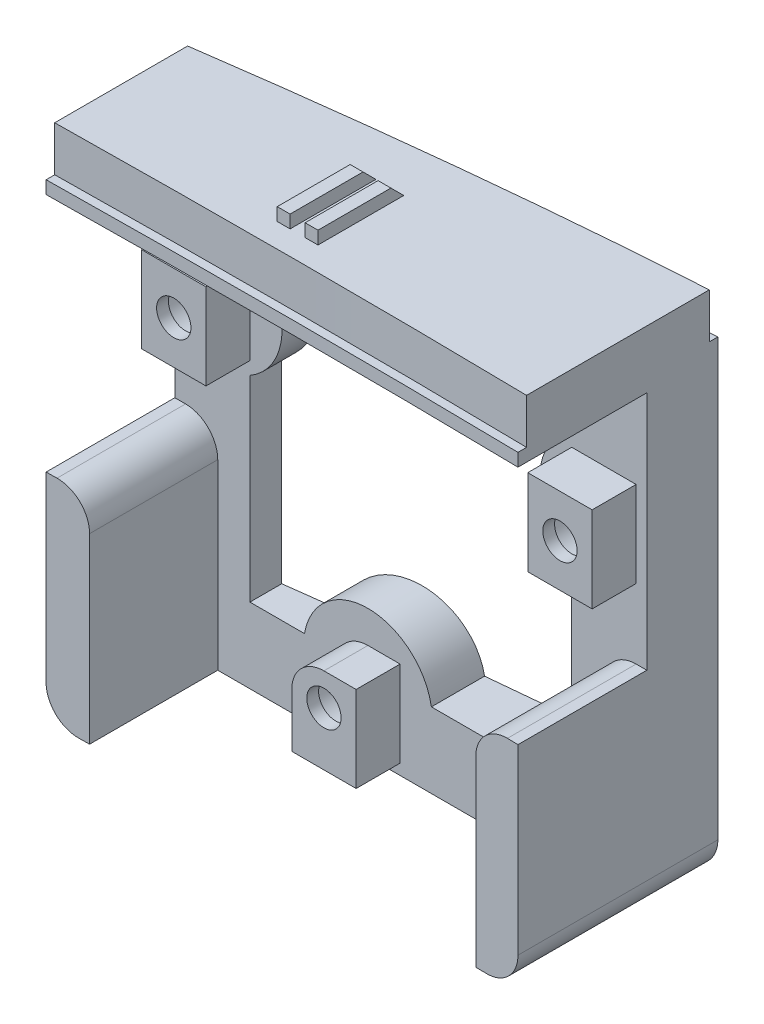
SolidWorks part; units mm, degrees
ref_plane "Front Plane" through (0, 0, 0) normal (0, 0, 1) x (1, 0, 0)
ref_plane "Top Plane" through (0, 0, 0) normal (0, 1, 0) x (1, 0, 0)
ref_plane "Right Plane" through (0, 0, 0) normal (1, 0, 0) x (0, 0, -1)
sketch "Sketch1" plane through (0, 0, 0) normal (0, 1, 0) x (1, 0, 0)
  line L0 (-144.1303, -12.9929) -> (155.8697, -12.8308) construction
  line L1 (-29.3738, 9.8314) -> (-29.3738, -4.1686)
  line L2 (14.6262, 14.4548) -> (14.6262, -4.183)
  line L5 (-29.3738, -2.9686) -> (14.6262, -2.9686)
  line L12 (-51.1303, 9.4041) -> (-59.1513, -7.7971) construction
  line L13 (-109.8536, -6.9996) -> (-109.986, -6.1605)
  line L14 (-11.0303, 7.0314) -> (-9.8303, 7.0314)
  line L15 (-11.0303, 7.0314) -> (-11.0303, -0.9686)
  line L16 (-11.0303, -0.9686) -> (-9.8303, -0.9686)
  line L17 (-9.8303, 7.0314) -> (-9.8303, -0.9686)
  line L18 (-8.4303, 7.0314) -> (-7.2303, 7.0314)
  line L19 (-8.4303, 7.0314) -> (-8.4303, -0.9686)
  line L20 (-8.4303, -0.9686) -> (-7.2303, -0.9686)
  line L21 (-7.2303, 7.0314) -> (-7.2303, -0.9686)
  circle A2 centre (-36.6303, 2.3202) radius 4.25
  arc A9 (-58.7697, -6.9788) -> (-58.7632, -6.9861) centre (-51.1303, -0.0856) ccw
  ellipse E0 centre (-36.6303, 2.3202) end of major axis (-36.1292, -4.0323) minor radius 5.05
  spline S0 degree 13 poles (-110.7235, -3.2524) (-98.8326, -0.2567) (-86.3944, 2.6358) (-73.4943, 5.427) (-60.2589, 8.0815) (-46.8275, 10.5453) (-33.3355, 12.7584) (-19.9065, 14.665) (-6.6486, 16.2187) (6.3449, 17.3865) (18.9944, 18.15) (31.2324, 18.5052) (43.0009, 18.4619) (54.25, 18.0415) knots 0.038912 0.038912 0.038912 0.038912 0.038912 0.038912 0.038912 0.038912 0.038912 0.038912 0.038912 0.038912 0.038912 0.038912 0.206425 0.206425 0.206425 0.206425 0.206425 0.206425 0.206425 0.206425 0.206425 0.206425 0.206425 0.206425 0.206425 0.206425
  spline S1 degree 3 poles (-105.7874, -5.9402) (-105.4515, -5.8576) (-103.7907, -5.4506) (-99.0842, -4.3142) (-91.5415, -2.5615) (-82.0457, -0.4684) (-69.1527, 2.2208) (-52.7063, 5.3568) (-32.7854, 8.6244) (-12.9944, 11.2716) (3.1558, 12.8711) (15.7533, 13.7541) (25.0163, 14.2135) (32.556, 14.4255) (38.4824, 14.4928) (41.3869, 14.4927) (42.8464, 14.4842) knots 0.043242 0.043242 0.043242 0.043242 0.044325 0.048583 0.058255 0.067926 0.077598 0.096941 0.116284 0.135628 0.154971 0.164642 0.174314 0.183986 0.188821 0.193657 0.193657 0.193657 0.193657
  spline S2 degree 3 poles (42.3412, -4.3021) (39.1703, -4.1474) (32.8439, -3.8739) (20.0493, -3.4589) (3.9637, -3.1861) (-15.3945, -3.1849) (-34.7131, -3.4228) (-53.9413, -3.8315) (-69.8279, -4.2978) (-82.3956, -4.7634) (-91.7251, -5.1693) (-99.1578, -5.5509) (-103.8174, -5.8207) (-105.4427, -5.9191) (-105.7874, -5.9402) knots 0.702444 0.702444 0.702444 0.702444 0.71714 0.731836 0.761227 0.790619 0.820011 0.849403 0.878795 0.89349 0.908186 0.922882 0.929138 0.930826 0.930826 0.930826 0.930826
  spline S3 degree 3 poles (-109.986, -6.1605) (-109.4642, -6.0291) (-108.4175, -5.7667) (-103.5943, -4.5692) (-94.8971, -2.4925) (-82.0108, 0.3758) (-63.7471, 4.1371) (-40.3543, 8.3552) (-16.9896, 11.6162) (1.2883, 13.4985) (14.7075, 14.5233) (27.7627, 15.1448) (36.8021, 15.2972) (42.0404, 15.2892) (43.1567, 15.2825) (43.6671, 15.2784) knots 0.038912 0.038912 0.038912 0.038912 0.040616 0.04232 0.054528 0.06816 0.081792 0.109056 0.13632 0.149952 0.163584 0.177216 0.190848 0.192861 0.194565 0.194565 0.194565 0.194565
  spline S4 degree 13 poles (52.5193, -8.6666) (40.2713, -7.9192) (27.7839, -7.3485) (15.1503, -6.9773) (2.4425, -6.804) (-10.2886, -6.8041) (-23.0116, -6.9375) (-35.7087, -7.1592) (-48.3688, -7.4339) (-60.9767, -7.7494) (-73.5011, -8.1244) (-85.8777, -8.6024) (-97.9897, -9.2254) (-109.6522, -9.993) knots 0.686195 0.686195 0.686195 0.686195 0.686195 0.686195 0.686195 0.686195 0.686195 0.686195 0.686195 0.686195 0.686195 0.686195 0.937578 0.937578 0.937578 0.937578 0.937578 0.937578 0.937578 0.937578 0.937578 0.937578 0.937578 0.937578 0.937578 0.937578
  spline S5 degree 3 poles (-110.5235, -4.0272) (-108.9029, -3.6189) (-105.6763, -2.8183) (-99.0735, -1.2268) (-90.6514, 0.7176) (-80.2925, 2.9758) (-67.9991, 5.4979) (-58.7506, 7.2436) (-50.652, 8.6798) (-47.6807, 9.1904) (-44.5606, 9.7093) (-38.2765, 10.745) (-25.0157, 12.7601) (-5.2278, 15.1631) (12.1229, 16.5847) (25.5727, 17.2429) (35.4177, 17.4948) (43.3901, 17.504) (49.633, 17.3925) (52.6803, 17.2987) (54.2127, 17.2415) knots 0.038912 0.038912 0.038912 0.038912 0.044146 0.049381 0.059851 0.07032 0.08079 0.096446 0.097403 0.1044 0.105092 0.106475 0.122668 0.143607 0.164546 0.175016 0.185486 0.195955 0.20119 0.206425 0.206425 0.206425 0.206425
  spline S6 degree 3 poles (52.5681, -7.868) (50.9024, -7.7664) (47.578, -7.5733) (40.8667, -7.2231) (32.4163, -6.8574) (22.195, -6.5335) (8.4979, -6.2488) (-8.6998, -6.1472) (-26.1679, -6.3047) (-37.8303, -6.5029) (-44.675, -6.6412) (-49.0049, -6.7375) (-53.5282, -6.8475) (-56.9797, -6.937) (-62.6027, -7.0912) (-70.3002, -7.3251) (-80.3346, -7.6831) (-90.3076, -8.1048) (-98.4897, -8.5174) (-104.9445, -8.8903) (-108.1134, -9.09) (-109.7048, -9.1947) knots 0.686195 0.686195 0.686195 0.686195 0.69405 0.701906 0.717617 0.733329 0.74904 0.780463 0.811886 0.82883 0.833892 0.843309 0.848739 0.854731 0.859237 0.874732 0.890444 0.906155 0.921867 0.929722 0.937578 0.937578 0.937578 0.937578
  spline S7 degree 3 poles (43.1189, -5.1414) (42.5664, -5.1139) (40.3515, -5.0059) (33.6908, -4.7068) (23.0612, -4.3421) (5.0464, -3.9837) (-17.5716, -3.9643) (-44.6283, -4.3923) (-66.9803, -4.9899) (-84.5965, -5.6437) (-96.3916, -6.1935) (-104.7586, -6.6717) (-108.8142, -6.9312) (-109.8536, -6.9996) knots 0.701175 0.701175 0.701175 0.701175 0.703751 0.711493 0.7321 0.752708 0.793923 0.835139 0.876354 0.896962 0.917569 0.932426 0.937578 0.937578 0.937578 0.937578
  spline S8 degree 3 poles (43.0791, -5.9404) (39.8994, -5.7822) (33.5559, -5.5021) (20.7207, -5.0752) (4.577, -4.7906) (-14.8622, -4.781) (-29.9542, -4.963) (-38.7515, -5.1226) (-41.4966, -5.1769) (-43.935, -5.226) (-46.8305, -5.2883) (-49.9812, -5.3611) (-51.9548, -5.4083) (-59.5635, -5.5969) (-69.6735, -5.894) (-82.18, -6.356) (-91.5501, -6.7627) (-99.2415, -7.157) (-105.3139, -7.5106) (-108.2984, -7.6991) (-109.7967, -7.7977) knots 0.701175 0.701175 0.701175 0.701175 0.71595 0.730726 0.760276 0.789826 0.819377 0.829214 0.830132 0.831967 0.840401 0.843428 0.846456 0.849484 0.878477 0.893252 0.908028 0.922803 0.93019 0.937578 0.937578 0.937578 0.937578
  spline S9 degree 3 poles (-110.1814, -5.3848) (-108.6794, -5.0063) (-105.6878, -4.2632) (-99.5742, -2.785) (-91.7846, -0.9758) (-82.2124, 1.1324) (-69.613, 3.7573) (-59.5108, 5.6872) (-50.135, 7.3499) (-46.7114, 7.9355) (-40.1955, 9.0106) (-29.5503, 10.6773) (-12.6029, 12.9298) (3.6765, 14.5228) (16.3735, 15.3941) (25.7087, 15.8415) (33.3064, 16.0409) (39.2778, 16.0967) (42.204, 16.0903) (43.6745, 16.0785) knots 0.038912 0.038912 0.038912 0.038912 0.043776 0.04864 0.058368 0.068097 0.077825 0.096092 0.09776 0.105207 0.106069 0.116738 0.136195 0.155652 0.16538 0.175108 0.184837 0.189701 0.194565 0.194565 0.194565 0.194565
  dimension "D1" = 8.5
  dimension "D2" = 14
  dimension "D3" = 44
  dimension "D4" = 1.2
  dimension "D5" = 26.8
  dimension "D6" = 28.2
  dimension "D7" = 8
  dimension "D8" = 8
  dimension "D9" = 2
  dimension "D10" = 2
  dimension "D11" = 1.2
  dimension "D12" = 1.2
extrude "Boss-Extrude2" add sketch "Sketch1" against normal blind 47.8 contours S3 L1 S1 L2 | S1 L1 L5 L2 | S2 L2 L5 L1 | S7 L2 S2 L1 | L17 L14 L15 L16 | L21 L18 L19 L20 region at (-7.4038, 0, -12.035) region at (-6.1165, 0, -4.438) region at (-7.397, 0, 3.1176) region at (-7.3732, 0, 3.6567) region at (-10.4303, 0, -3.0314) region at (-7.8303, 0, -3.0314)
extrude "Cut-Extrude1" cut sketch "Sketch1<3>" against normal blind 4.2 contours S7 L2 S2 L1 | S3 L1 S1 L2 region at (-7.4038, 0, -12.035) region at (-7.3732, 0, 3.6567)
sketch "Sketch1<3>" plane through (0, 0, 0) normal (0, 1, 0) x (1, 0, 0) same geometry as "Sketch1"
sketch "Sketch2" plane through (0, 0, 0) normal (0, 1, 0) x (1, 0, 0)
  line L0 (-29.3738, 7.8314) -> (14.6262, 7.8314)
  line L1 (-29.3738, 9.8314) -> (-29.3738, -4.1686) construction
  line L2 (14.6262, 14.4548) -> (14.6262, -4.183) construction
  line L3 (-29.3738, -2.9686) -> (14.6262, -2.9686) construction
  line L4 (-29.3738, -2.9686) -> (14.6262, -2.9686)
  line L5 (14.6262, 14.4548) -> (14.6262, -4.183)
  line L6 (-29.3738, 9.8314) -> (-29.3738, -4.1686)
  spline S0 degree 3 poles (-1947.4588, -167.681) (424.4026, -117.2665) (271.9813, -15.4064) (33.6908, -4.7068) (23.0612, -4.3421) (5.0464, -3.9837) (-17.5716, -3.9643) (-44.6283, -4.3923) (-66.9803, -4.9899) (-84.5965, -5.6437) (-96.3916, -6.1935) (-281.2066, -16.7558) (-334.7502, -73.0291) (1880.8527, -187.1354) knots -0.374252 -0.374252 -0.374252 -0.374252 0.703751 0.711493 0.7321 0.752708 0.793923 0.835139 0.876354 0.896962 0.917569 0.932426 1.794118 1.794118 1.794118 1.794118 only from (43.1189, -5.1414) to (-109.8536, -6.9996) construction
  spline S1 degree 3 poles (43.1189, -5.1414) (42.5664, -5.1139) (40.3515, -5.0059) (33.6908, -4.7068) (23.0612, -4.3421) (5.0464, -3.9837) (-17.5716, -3.9643) (-44.6283, -4.3923) (-66.9803, -4.9899) (-84.5965, -5.6437) (-96.3916, -6.1935) (-104.7586, -6.6717) (-108.8142, -6.9312) (-109.8536, -6.9996) knots 0.701175 0.701175 0.701175 0.701175 0.703751 0.711493 0.7321 0.752708 0.793923 0.835139 0.876354 0.896962 0.917569 0.932426 0.937578 0.937578 0.937578 0.937578
  spline M3 degree 3 poles (-105.7874, -5.9402) (-105.4427, -5.9191) (-103.8174, -5.8207) (-99.1578, -5.5509) (-91.7251, -5.1693) (-82.3956, -4.7634) (-69.8279, -4.2978) (-53.9413, -3.8315) (-34.7131, -3.4228) (-15.3945, -3.1849) (3.9637, -3.1861) (20.0493, -3.4589) (32.8439, -3.8739) (39.1703, -4.1474) (42.3412, -4.3021) knots 0.702444 0.702444 0.702444 0.702444 0.704132 0.710388 0.725084 0.739779 0.754475 0.783867 0.813259 0.842651 0.872042 0.901434 0.91613 0.930826 0.930826 0.930826 0.930826 only from (-29.3738, -3.3687) to (14.6262, -3.383)
  line M4 (14.6262, -3.383) -> (14.6262, 13.6533)
  line M6 (-29.3738, 9.0233) -> (-29.3738, -3.3687)
  dimension "D1" = 2
extrude "Cut-Extrude2" cut sketch "Sketch2" against normal through all from offset 5.4 contours L4 L0 M6 M4 | L4 M6 M3 M4 | S1 L5 L6 M3 region at (-7.3738, 0, -2.4314) region at (-7.3795, 0, 3.5139) offset against normal yes
sketch "Sketch3" plane through (0, 0, -7.8314) normal (0, 0, 1) x (1, 0, 0)
  line L0 (14.6262, -47.8) -> (14.6262, -5.4) construction
  line L1 (-29.3738, -47.8) -> (14.6262, -47.8) construction
  circle A0 centre (-11.3738, -41.8) radius 2.5
  circle A1 centre (-25.3738, -17.3) radius 2.5
  circle A2 centre (10.6262, -17.3) radius 2.5
  dimension "D1" = 5
  dimension "D2" = 14
  dimension "D3" = 36
  dimension "D4" = 4
  dimension "D5" = 24.5
  dimension "D6" = 6
extrude "Cut-Extrude3" cut sketch "Sketch3" against normal through all
sketch "Sketch4" plane through (0, 0, -7.8314) normal (0, 0, 1) x (1, 0, 0)
  line L0 (-28.3738, -13.3) -> (-22.3738, -13.3)
  line L1 (-28.3738, -13.3) -> (-28.3738, -21.3)
  line L2 (-28.3738, -21.3) -> (-22.3738, -21.3)
  line L3 (-22.3738, -13.3) -> (-22.3738, -21.3)
  line L4 (7.6262, -13.3) -> (13.6262, -13.3)
  line L5 (7.6262, -13.3) -> (7.6262, -21.3)
  line L6 (7.6262, -21.3) -> (13.6262, -21.3)
  line L7 (13.6262, -13.3) -> (13.6262, -21.3)
  line L9 (-14.3738, -41.8) -> (-14.3738, -46.8)
  line L10 (-14.3738, -46.8) -> (-8.3738, -46.8)
  line L11 (-8.3738, -38.8) -> (-8.3738, -46.8)
  line L12 (-29.3738, -47.8) -> (-29.3738, -5.4) construction
  line L13 (14.6262, -47.8) -> (14.6262, -5.4) construction
  line L14 (-29.3738, -47.8) -> (14.6262, -47.8) construction
  line L15 (-11.3738, -38.8) -> (-8.3738, -38.8)
  arc A0 (-11.3738, -38.8) -> (-14.3738, -41.8) centre (-11.3738, -41.8) ccw
  point P23 (-25.3738, -21.3)
  dimension "D11" = 28.5
  dimension "D12" = 3
  dimension "D1" = 1
  dimension "D2" = 8
  dimension "D3" = 6
  dimension "D4" = 6
  dimension "D5" = 8
  dimension "D6" = 1
  dimension "D7" = 1
  dimension "D8" = 8
  dimension "D9" = 6
  dimension "D10" = 14
extrude "Boss-Extrude4" add sketch "Sketch4" along normal blind 4.1
sketch "Sketch8" plane through (0, 0, -7.8314) normal (0, 0, 1) x (1, 0, 0)
  circle A0 centre (10.6262, -17.3) radius 1.6
  circle A1 centre (-25.3738, -17.3) radius 1.6
  circle A2 centre (-11.3738, -41.8) radius 1.6
  dimension "D1" = 3.2
extrude "Cut-Extrude6" cut sketch "Sketch8" against normal through all both and the other way through all
ref_plane "Plane3" through (0, 0, -4.8314) normal (0, 0, 1) x (1, 0, 0)
ref_plane "Plane1" through (0, 0, -8.0314) normal (0, 0, 1) x (1, 0, 0)
sketch "Sketch9" plane through (0, 0, -8.0314) normal (0, 0, 1) x (1, 0, 0)
  circle A0 centre (10.6262, -17.3) radius 2.5
  circle A1 centre (-25.3738, -17.3) radius 2.5
  circle A2 centre (-11.3738, -41.8) radius 2.5
  dimension "D1" = 5
ref_plane "Plane2" through (0, 0, -9.0314) normal (0, 0, 1) x (1, 0, 0)
sketch "Sketch10" plane through (0, 0, -9.0314) normal (0, 0, 1) x (1, 0, 0)
  circle A0 centre (10.6262, -17.3) radius 2.7
  circle A1 centre (-11.3738, -41.8) radius 2.7
  circle A2 centre (-25.3738, -17.3) radius 2.7
  dimension "D1" = 5.4
loft "Cut-Loft2" cut section "Sketch9" section "Sketch10" connector at (9.6622, -19.6067, -8.0314) connector at (10.8262, -19.9926, -9.0314)
loft "Cut-Loft3" cut section "Sketch10<8>" section "Sketch9<8>" connector at (-23.8675, -15.0593, -9.0314) connector at (-23.8366, -15.3285, -8.0314)
sketch "Sketch10<8>" plane through (0, 0, -9.0314) normal (0, 0, 1) x (1, 0, 0) same geometry as "Sketch10"
sketch "Sketch9<8>" plane through (0, 0, -8.0314) normal (0, 0, 1) x (1, 0, 0) same geometry as "Sketch9"
loft "Cut-Loft4" cut section "Sketch10<9>" section "Sketch9<9>" connector at (-9.5256, -39.8318, -9.0314) connector at (-9.7018, -39.9414, -8.0314)
sketch "Sketch10<9>" plane through (0, 0, -9.0314) normal (0, 0, 1) x (1, 0, 0) same geometry as "Sketch10"
sketch "Sketch9<9>" plane through (0, 0, -8.0314) normal (0, 0, 1) x (1, 0, 0) same geometry as "Sketch9"
sketch "Sketch12" plane through (0, 0, -4.8314) normal (0, 0, 1) x (1, 0, 0)
  circle A1 centre (-25.3738, -17.3) radius 2.5
  circle A2 centre (10.6262, -17.3) radius 2.5
  circle A3 centre (-11.3738, -41.8) radius 2.5
  dimension "D1" = 5
extrude "Cut-Extrude10" cut sketch "Sketch12" against normal through all
sketch "Sketch13" plane through (0, 0, -7.8314) normal (0, 0, 1) x (1, 0, 0)
  circle A0 centre (-25.3738, -17.3) radius 3
  circle A1 centre (10.6262, -17.3) radius 3
  circle A2 centre (-11.3738, -41.8) radius 3
  dimension "D1" = 6
extrude "Cut-Extrude11" cut sketch "Sketch13" against normal through all from surface starting at plane "Plane2"
sketch "Sketch14" plane through (0, 0, -7.8314) normal (0, 0, 1) x (1, 0, 0)
  line L0 (-22.3738, -21.3) -> (-22.3738, -13.3) construction
  line L1 (-22.3738, -6.2) -> (7.6262, -6.2)
  line L2 (-22.3738, -6.2) -> (-22.3738, -40.8)
  line L3 (-22.3738, -40.8) -> (7.6262, -40.8)
  line L4 (7.6262, -6.2) -> (7.6262, -40.8)
  line L6 (7.6262, -13.3) -> (7.6262, -21.3) construction
  line L7 (-29.3738, -5.4) -> (14.6262, -5.4) construction
  line L8 (-29.3738, -47.8) -> (14.6262, -47.8) construction
  circle A0 centre (-11.3738, -41.8) radius 6
  circle A1 centre (-25.3738, -17.3) radius 6
  circle A2 centre (10.6262, -17.3) radius 6
  dimension "D3" = 12
  dimension "D1" = 0.8
  dimension "D2" = 7
extrude "Cut-Extrude15" cut sketch "Sketch14" against normal through all contours A2 L4 L1 L2 A1 L3 A0 region at (-7.1859, -23.0743, -7.8314)
extrude "Boss-Extrude5" add sketch "Sketch1<4>" along normal blind 1.2 contours L17 L14 L15 L16 | L21 L18 L19 L20 region at (-10.4303, 0, -3.0314) region at (-7.8303, 0, -3.0314)
sketch "Sketch1<4>" plane through (0, 0, 0) normal (0, 1, 0) x (1, 0, 0) same geometry as "Sketch1"
sketch "Sketch16" plane through (0, 0, 0) normal (0, 1, 0) x (1, 0, 0)
  line L0 (-29.3738, 7.8314) -> (14.6262, 7.8314) construction
  line L1 (-29.3738, 7.8314) -> (14.6262, 7.8314)
  line L2 (-28.1738, 7.8314) -> (-28.1738, -3.3521)
  line L3 (13.4262, 7.8314) -> (13.4262, -3.3616)
  line L4 (-29.3738, 9.0233) -> (-29.3738, -3.3687) construction
  line L5 (14.6262, 13.6533) -> (14.6262, -3.383) construction
  line L6 (-11.0303, 7.8314) -> (-11.0303, -2.0043)
  line L7 (-7.2303, 7.8314) -> (-7.2303, -1.9972)
  line L8 (-11.0303, 7.0314) -> (-11.0303, -0.9686) construction
  line L9 (-7.2303, 7.0314) -> (-7.2303, -0.9686) construction
  line L10 (-11.0303, 7.8314) -> (-28.1738, -2.152) construction
  line L11 (-7.2303, 7.8314) -> (13.4262, -2.1614) construction
  line L12 (-11.3322, 8.3499) -> (-28.4758, -1.6335)
  line L13 (-10.7284, 7.313) -> (-27.8719, -2.6705)
  line L14 (-7.4916, 7.2913) -> (13.1649, -2.7016)
  line L15 (-6.969, 8.3716) -> (13.6875, -1.6213)
  circle A0 centre (-11.0303, 7.8314) radius 0.6
  circle A1 centre (-7.2303, 7.8314) radius 0.6
  circle A2 centre (13.4262, -2.1614) radius 0.6
  circle A3 centre (-28.1738, -2.152) radius 0.6
  spline S0 degree 3 poles (-911.8741, -1709.024) (611.2322, -138.1951) (312.6294, -3.2064) (-384.575, -3.1606) (-743.4746, -142.8958) (590.663, 1832.5542) knots -0.674113 -0.674113 -0.674113 -0.674113 0.761227 0.790619 2.5016 2.5016 2.5016 2.5016 only from (14.6262, -3.383) to (-29.3738, -3.3687) construction
  spline S1 degree 3 poles (14.6262, -3.383) (11.0735, -3.3176) (1.077, -3.186) (-13.6131, -3.185) (-24.7175, -3.3027) (-29.3738, -3.3687) knots 0.744984 0.744984 0.744984 0.744984 0.761227 0.790619 0.811897 0.811897 0.811897 0.811897
  spline S2 degree 1 poles (14.6482, -2.1832) (-29.3908, -2.1688) knots 0 0 1 1 construction
  spline S3 degree 3 poles (14.6482, -2.1832) (14.3424, -2.1776) (13.8336, -2.1684) (10.1691, -2.1054) (3.5012, -2.0233) (-3.6044, -1.9952) (-7.8637, -1.9974) (-9.1304, -1.9994) (-10.397, -2.0022) (-13.4845, -2.0121) (-19.4178, -2.0479) (-24.9153, -2.1078) (-28.5796, -2.1575) (-29.0863, -2.1645) (-29.3908, -2.1688) knots 0.744984 0.744984 0.744984 0.744984 0.746379 0.747309 0.761712 0.776781 0.779665 0.781107 0.78255 0.785434 0.795169 0.809581 0.810507 0.811897 0.811897 0.811897 0.811897
  dimension "D4" = 1.2
  dimension "D1" = 1.2
  dimension "D2" = 1.2
  dimension "D3" = 1.2
  dimension "D5" = 0.6
  dimension "D6" = 0.6
  dimension "D7" = 0.6
  dimension "D8" = 0.6
sketch "Sketch17" plane through (0, -5.4, 0) normal (0, -1, 0) x (1, 0, 0)
  line L1 (-29.3738, -7.8314) -> (-25.3738, -7.8314)
  line L2 (-29.3738, -7.8314) -> (-29.3738, 4.1686)
  line L4 (-25.3738, -7.8314) -> (-25.3738, 4.116)
  line L5 (14.6262, -7.8314) -> (10.6262, -7.8314)
  line L6 (14.6262, -7.8314) -> (14.6262, 4.183)
  line L8 (10.6262, -7.8314) -> (10.6262, 4.1171)
  spline S1 degree 3 poles (-1439.9508, 1327.7295) (571.77, 134.6459) (296.7394, 4.2338) (-397.6226, 3.6384) (-768.3734, 148.9839) (877.1569, -1722.2564) knots -0.596734 -0.596734 -0.596734 -0.596734 0.752708 0.793923 2.566496 2.566496 2.566496 2.566496 only from (14.6262, 4.183) to (-29.3738, 4.1686) construction
  spline S2 degree 3 poles (14.6262, 4.183) (12.9332, 4.1518) (2.2231, 3.9812) (-12.4727, 3.9686) (-25.4391, 4.1127) (-29.3738, 4.1686) knots 0.744962 0.744962 0.744962 0.744962 0.752708 0.793923 0.81191 0.81191 0.81191 0.81191
  line M5 (11.9997, 2.1379) -> (-7.2303, -7.1649)
  spline M7 degree 3 poles (14.6482, 2.1832) (14.3424, 2.1776) (13.8336, 2.1684) (10.1691, 2.1054) (3.5012, 2.0233) (-3.6044, 1.9952) (-7.8637, 1.9974) (-9.1304, 1.9994) (-10.397, 2.0022) (-13.4845, 2.0121) (-19.4178, 2.0479) (-24.9153, 2.1078) (-28.5796, 2.1575) (-29.0863, 2.1645) (-29.3908, 2.1688) knots 0.744984 0.744984 0.744984 0.744984 0.746379 0.747309 0.761712 0.776781 0.779665 0.781107 0.78255 0.785434 0.795169 0.809581 0.810507 0.811897 0.811897 0.811897 0.811897 only from (-7.2303, 1.9972) to (11.9997, 2.1379)
  line M8 (13.4262, 1.4949) -> (13.4262, -7.8314)
  line M9 (13.4262, -7.8314) -> (14.6262, -7.8314)
  line M10 (14.6262, -7.8314) -> (14.6262, 4.183)
  spline M11 degree 3 poles (43.1189, 5.1414) (42.5664, 5.1139) (40.3515, 5.0059) (33.6908, 4.7068) (23.0612, 4.3421) (5.0464, 3.9837) (-17.5716, 3.9643) (-44.6283, 4.3923) (-66.9803, 4.9899) (-84.5965, 5.6437) (-96.3916, 6.1935) (-104.7586, 6.6717) (-108.8142, 6.9312) (-109.8536, 6.9996) knots 0.701175 0.701175 0.701175 0.701175 0.703751 0.711493 0.7321 0.752708 0.793923 0.835139 0.876354 0.896962 0.917569 0.932426 0.937578 0.937578 0.937578 0.937578 only from (14.6262, 4.183) to (-29.3738, 4.1686)
  line M12 (-29.3738, 4.1686) -> (-29.3738, -7.8314)
  line M13 (-29.3738, -7.8314) -> (-28.1738, -7.8314)
  line M14 (-28.1738, -7.8314) -> (-28.1738, 1.4577)
  line M15 (-28.1738, 1.4577) -> (-12.2226, -7.8314)
  line M17 (-5.8525, -7.8314) -> (13.4262, 1.4949)
  line M19 (-11.0303, -7.1371) -> (-26.9538, 2.1358)
  spline M20 degree 3 poles (14.6482, 2.1832) (14.3424, 2.1776) (13.8336, 2.1684) (10.1691, 2.1054) (3.5012, 2.0233) (-3.6044, 1.9952) (-7.8637, 1.9974) (-9.1304, 1.9994) (-10.397, 2.0022) (-13.4845, 2.0121) (-19.4178, 2.0479) (-24.9153, 2.1078) (-28.5796, 2.1575) (-29.0863, 2.1645) (-29.3908, 2.1688) knots 0.744984 0.744984 0.744984 0.744984 0.746379 0.747309 0.761712 0.776781 0.779665 0.781107 0.78255 0.785434 0.795169 0.809581 0.810507 0.811897 0.811897 0.811897 0.811897 only from (-26.9538, 2.1358) to (-11.0303, 2.0043)
  dimension "D1" = 4
  dimension "D2" = 4
extrude "Boss-Extrude6" add sketch "Sketch17" against normal blind 20 from surface contours L1 L4 M15 M14 | L8 L5 M8 M17 | L4 M15 M19 M20 M11 M12 M13 M14 | L8 M17 M8 M9 M10 M11 M7 M5 | L8 M5 M7 | L4 M19 M20 region at (-29.2473, -5.4, -1.8314) region at (12.6283, -5.4, 4.0215) region at (-26.8187, -5.4, -3.5815) region at (12.0627, -5.4, -3.4981) starting at face at (-12.8738, -47.8, -10.4873)
fillet "Fillet1" radius 3 4 edges at (10.6262, -27.8, -1.8572) (-25.3738, -27.8, -1.8577)
sketch "Sketch19" plane through (14.6262, 0, 0) normal (1, 0, 0) x (0, 0, -1)
  line L0 (-2.983, -43.6) -> (-2.983, -29)
  line L1 (-2.983, -29) -> (5.2761, -43.6)
  line L2 (5.2761, -43.6) -> (-2.983, -43.6)
  line L3 (-1.6043, -29) -> (6.6548, -43.6)
  line L8 (-1.6043, -29) -> (6.6548, -29)
  line L9 (6.6548, -29) -> (6.6548, -43.6)
  line L10 (-4.183, -44.8) -> (14.4548, -44.8) construction
  line L11 (-4.183, -27.8) -> (-4.183, -44.8) construction
  line L12 (7.8314, -27.8) -> (-4.183, -27.8) construction
  line L14 (14.4548, -44.8) -> (14.4548, -4.2) construction
  dimension "D1" = 1.2
  dimension "D2" = 1.2
  dimension "D3" = 1.2
  dimension "D4" = 1.2
  dimension "D5" = 1.2
  dimension "D6" = 1.2
  dimension "D7" = 7.8
sketch "Sketch20" plane through (-29.3738, 0, 0) normal (-1, 0, 0) x (0, 0, 1)
  line L0 (-6.6314, -43.6) -> (-6.6314, -29)
  line L1 (-6.6314, -29) -> (1.5913, -43.6)
  line L2 (1.5913, -43.6) -> (-6.6314, -43.6)
  line L3 (-5.2542, -29) -> (2.9686, -43.6)
  line L8 (-5.2542, -29) -> (2.9686, -29)
  line L9 (2.9686, -29) -> (2.9686, -43.6)
  line L13 (4.1686, -27.8) -> (4.1686, -44.8) construction
  line L15 (4.1686, -27.8) -> (-7.8314, -27.8) construction
  line L17 (-9.8314, -44.8) -> (-9.8314, -4.2) construction
  line L18 (-9.8314, -44.8) -> (4.1686, -44.8) construction
  dimension "D1" = 1.2
  dimension "D2" = 1.2
  dimension "D3" = 1.2
  dimension "D4" = 3.2
  dimension "D5" = 1.2
  dimension "D6" = 1.2
  dimension "D7" = 1.2
chamfer "Chamfer1" distance 1.2 angle 45 2 edges at (-7.8303, 1.2, -7.0314) (-10.4303, 1.2, -7.0314)
